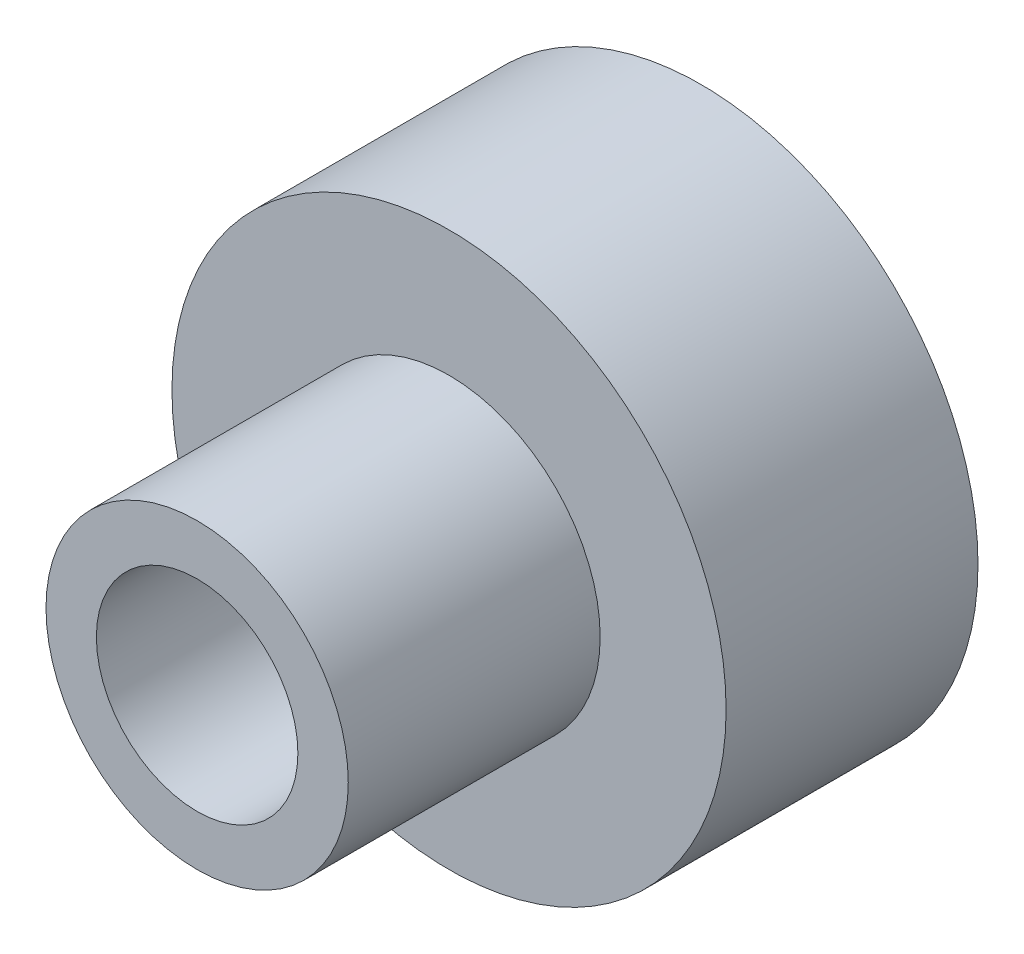
SolidWorks part; units mm, degrees
ref_plane "Front Plane" through (0, 0, 0) normal (0, 0, 1) x (1, 0, 0)
ref_plane "Top Plane" through (0, 0, 0) normal (0, 1, 0) x (1, 0, 0)
ref_plane "Right Plane" through (0, 0, 0) normal (1, 0, 0) x (0, 0, -1)
sketch "Sketch1" plane through (0, 0, 0) normal (0, 0, 1) x (1, 0, 0)
  circle A0 centre (0, 0) radius 20
  circle A1 centre (0, 0) radius 42.5
  circle A2 centre (0, 0) radius 55
  circle A3 centre (0, 0) radius 30
  dimension "D1" = 40
  dimension "D2" = 85
extrude "Boss-Extrude1" add sketch "Sketch1" along normal blind 50 contours A3
extrude "Boss-Extrude2" add sketch "Sketch1<4>" against normal blind 50 separate body contours A2 A1 | A1 A3 region at (-41.2979, 0, 0) region at (-53.4444, 0, 0)
sketch "Sketch1<4>" plane through (0, 0, 0) normal (0, 0, 1) x (1, 0, 0) same geometry as "Sketch1"
sketch "Sketch2" plane through (0, 0, 50) normal (0, 0, 1) x (1, 0, 0)
  circle A0 centre (0, 0) radius 20
extrude "Cut-Extrude1" cut sketch "Sketch2" against normal through all
sketch "Sketch3" plane through (0, 0, -50) normal (0, 0, -1) x (-1, 0, 0)
  circle A0 centre (0, 0) radius 42.5
  dimension "D1" = 85
extrude "Cut-Extrude2" cut sketch "Sketch3" against normal blind 40
